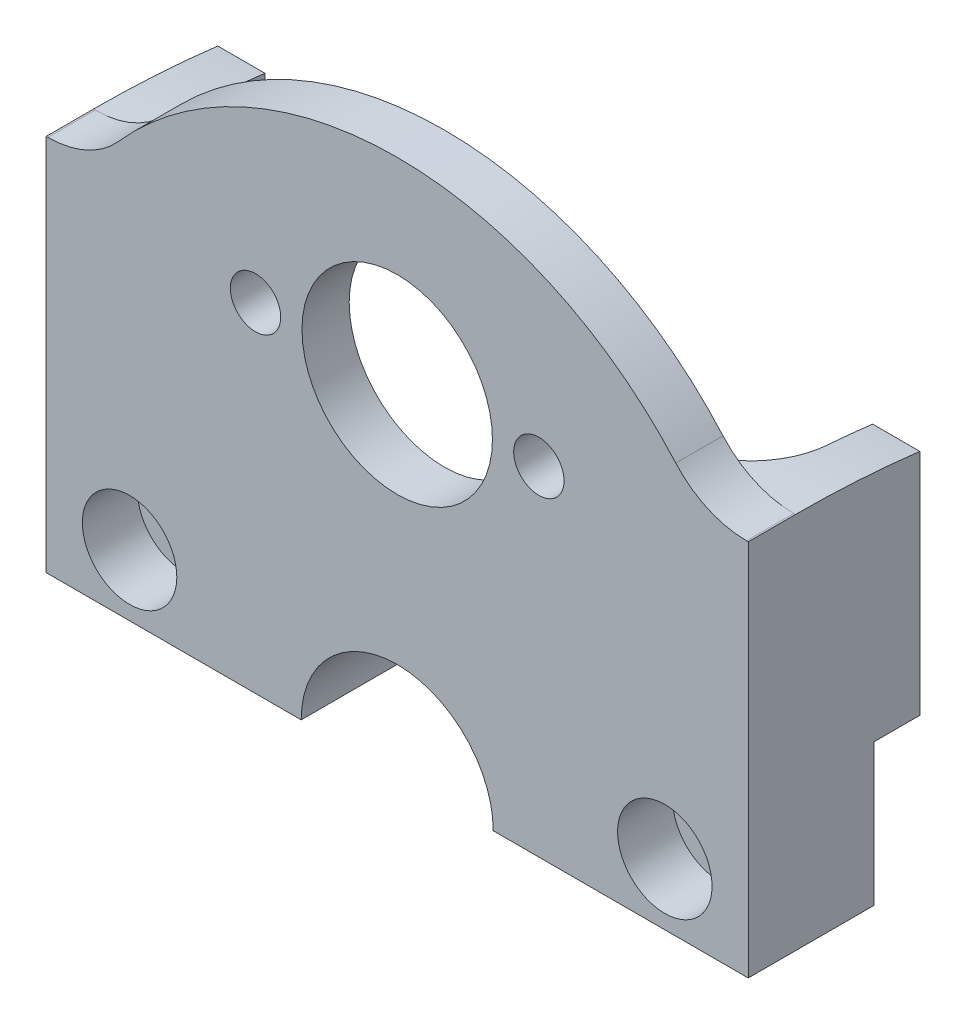
SolidWorks part; units mm, degrees
material "ABS"
ref_plane "正面" through (0, 0, 0) normal (0, 0, 1) x (1, 0, 0)
ref_plane "平面" through (0, 0, 0) normal (0, 1, 0) x (1, 0, 0)
ref_plane "右側面" through (0, 0, 0) normal (1, 0, 0) x (0, 0, -1)
sketch "ｽｹｯﾁ2" plane through (0, 0, 0) normal (0, 0, 1) x (1, 0, 0)
  line L0 (0, -18.7) -> (0, 18.7) construction
  line L1 (-9, 36.4) -> (9, 36.4) construction
  line L2 (0, 17) -> (0, 0) construction
  line L3 (-22.3, 23.9) -> (-22.3, 14.9)
  line L4 (-22.3, 48.9) -> (22.3, 48.9) construction
  line L5 (-22.3, 48.9) -> (-22.3, 23.9) construction
  line L6 (-22.3, 23.9) -> (22.3, 23.9)
  line L7 (22.3, 48.9) -> (22.3, 23.9) construction
  line L8 (-22.3, 48.9) -> (22.3, 23.9) construction
  line L9 (-22.3, 23.9) -> (22.3, 48.9) construction
  line L10 (-22.3, 14.9) -> (22.3, 14.9)
  line L11 (22.3, 14.9) -> (22.3, 23.9)
  line L12 (-22.3, 38.9) -> (-22.3, 23.9)
  line L13 (22.3, 38.9) -> (22.3, 23.9)
  line L14 (-22.3, 38.9) -> (-19.3, 38.9)
  line L15 (19.3, 38.9) -> (22.3, 38.9)
  line L16 (-17, 18.8) -> (17, 18.8) construction
  line L17 (-25, -15) -> (25, -15) construction
  line L18 (-25, -15) -> (-25, 23.9) construction
  line L19 (-25, 23.9) -> (25, 23.9) construction
  line L20 (25, -15) -> (25, 23.9) construction
  line L21 (-25, -15) -> (25, 23.9) construction
  line L22 (-25, 23.9) -> (25, -15) construction
  circle A0 centre (0, 0) radius 21.5 construction
  circle A1 centre (0, 0) radius 10.25 construction
  circle A2 centre (0, 36.4) radius 6.05
  circle A3 centre (-9, 36.4) radius 1.6
  circle A4 centre (9, 36.4) radius 1.6
  circle A6 centre (0, 0) radius 17 construction
  circle A9 centre (0, 17) radius 4 construction
  circle A10 centre (0, 36.4) radius 12.5 construction
  arc A11 (-6.1, 14.9) -> (6.1, 14.9) centre (0, 14.9) cw
  arc A12 (-19.3, 38.9) -> (19.3, 38.9) centre (0, 25.2755) cw
  circle A13 centre (-17, 18.8) radius 1.6
  circle A14 centre (17, 18.8) radius 1.6
  point P10 (0, 36.4)
  point P14 (0, 0)
  point P19 (0, 0)
  point P33 (0, 18.8)
  dimension "D1" = 12.1
  dimension "D2" = 3.2
  dimension "D3" = 43
  dimension "D4" = 34
  dimension "D5" = 20.5
  dimension "D8" = 25
  dimension "D12" = 8
  dimension "D6" = 36.4
  dimension "D7" = 18
  dimension "D10" = 25
  dimension "D11" = 9
  dimension "D13" = 15
  dimension "D14" = 3
  dimension "D15" = 50
  dimension "D9" = 2.7
  dimension "D16" = 8
  dimension "D17" = 5.1
  dimension "D18" = 15
  dimension "D19" = 38.9
extrude "ﾎﾞｽ - 押し出し1" add sketch "ｽｹｯﾁ2" against normal blind 3 contours L7 L4 L5 L6 A4 A3 A2 region at (-21.7887, 31.4, 0)
extrude "ﾎﾞｽ - 押し出し2" add sketch "ｽｹｯﾁ2<3>" against normal blind 8 contours L10 L11 L6 L3 region at (0, 23.445, 0)
sketch "ｽｹｯﾁ2<3>" plane through (0, 0, 0) normal (0, 0, 1) x (1, 0, 0) same geometry as "ｽｹｯﾁ2"
sketch "ｽｹｯﾁ3" plane through (-22.3, 0, 0) normal (-1, 0, 0) x (0, 0, 1)
  line L0 (-8, 23.9) -> (-10.9, 23.9)
  line L1 (-8, 23.9) -> (-43, 23.9) construction
  line L2 (-43, 23.9) -> (-43, 20.1209) construction
  line L3 (-3, 38.9) -> (0, 38.9) construction
  line L4 (-43, 16.1209) -> (-10.9, 16.1209)
  line L5 (-8, 23.9) -> (-3, 23.9)
  line L6 (-3, 23.9) -> (-3, 38.9)
  line L7 (-10.9, 16.1209) -> (-10.9, 23.9)
  arc A1 (-43, 16.1209) -> (-45.6008, 23.16) centre (-43, 20.1209) cw
  arc A2 (-45.6008, 23.16) -> (-3, 38.9) centre (-3, -26.62) cw
  circle A3 centre (-43, 20.1209) radius 1.65
  dimension "D2" = 3.3
  dimension "D3" = 4
  dimension "D1" = 2.9
  dimension "D4" = 35
  dimension "D5" = 3.7791
extrude "ﾎﾞｽ - 押し出し4" add sketch "ｽｹｯﾁ3" against normal blind 3
mirror "ﾐﾗｰ11" about plane through (0, 0, 0) normal (1, 0, 0) of "ﾎﾞｽ - 押し出し4"
fillet "ﾌｨﾚｯﾄ8" [suppressed] radius 3
fillet "ﾌｨﾚｯﾄ9" [suppressed] radius 3
sketch "ｽｹｯﾁ5" plane through (0, 0, 0) normal (0, 0, 1) x (1, 0, 0)
  circle A0 centre (-17, 18.8) radius 3
  circle A1 centre (17, 18.8) radius 3
  dimension "D1" = 6
extrude "ｶｯﾄ - 押し出し1" cut sketch "ｽｹｯﾁ5" against normal blind 3.5
sketch "ｽｹｯﾁ6" plane through (-22.3, 0, 0) normal (-1, 0, 0) x (0, 0, 1)
  line L0 (-43, 16.1209) -> (-10.9, 16.1209) construction
  line L1 (-66.2053, 67.203) -> (-10.9, 67.203)
  line L2 (-66.2053, 67.203) -> (-66.2053, 16.1209)
  line L3 (-66.2053, 16.1209) -> (-10.9, 16.1209)
  line L4 (-10.9, 67.203) -> (-10.9, 16.1209)
  line L5 (-66.2053, 67.203) -> (-10.9, 16.1209) construction
  line L6 (-66.2053, 16.1209) -> (-10.9, 67.203) construction
  point P0 (-38.5526, 41.6619)
  point P5 (0, 0)
  point P7 (0, 0)
  point P8 (-10.9, 16.1209)
  point P11 (-13.0796, 16.1209)
  point P13 (0, 0)
extrude "ｶｯﾄ - 押し出し2" cut sketch "ｽｹｯﾁ6" against normal through all
fillet "ﾌｨﾚｯﾄ10" radius 6 2 edges at (19.3, 38.9, -1.5) (-19.3, 38.9, -1.5)
fillet "ﾌｨﾚｯﾄ11" radius 5 2 edges at (19.3, 31.4, -3) (-19.3, 31.4, -3)
equation "\"D6@ｽｹｯﾁ2\"=(65+26)*0.8/2"
equation "\"D5@ｽｹｯﾁ3\"=39/2-20*sin(50)-0.4"
